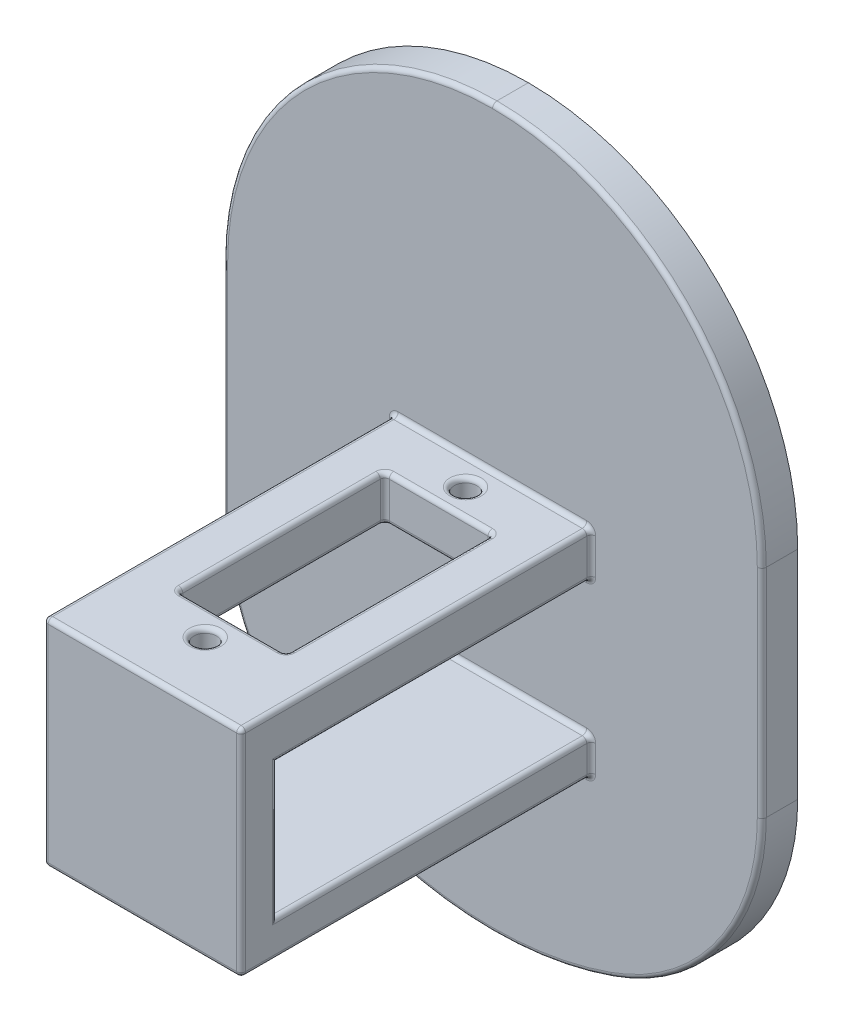
SolidWorks part; units mm, degrees
ref_plane "Front Plane" through (0, 0, 0) normal (0, 0, 1) x (1, 0, 0)
ref_plane "Top Plane" through (0, 0, 0) normal (0, 1, 0) x (1, 0, 0)
ref_plane "Right Plane" through (0, 0, 0) normal (1, 0, 0) x (0, 0, -1)
sketch "Sketch1" plane through (0, 0, 0) normal (0, 0, 1) x (1, 0, 0)
  circle A0 centre (0, 0) radius 40
  point P0 (0, 0)
  dimension "D1" = 80
extrude "Boss-Extrude1" add sketch "Sketch1" along normal blind 4
sketch "Sketch10" plane through (0, 0, 4) normal (0, 0, 1) x (1, 0, 0)
  line L0 (-30, 26.4575) -> (-30, -26.4575)
  line L1 (30, 26.4575) -> (30, -26.4575)
  arc A0 (30, -26.4575) -> (30, 26.4575) centre (0, 0) ccw
  circle A1 centre (0, 0) radius 40
  arc A2 (-30, 26.4575) -> (-30, -26.4575) centre (0, 0) ccw
  dimension "D2" = 30
  dimension "D3" = 60
  dimension "D1" = 0
extrude "Cut-Extrude3" cut sketch "Sketch10" against normal blind 10
fillet "Fillet1" radius 30 2 edges at (-30, 26.4575, 2) (30, 26.4575, 2)
fillet "Fillet2" radius 25 2 edges at (-30, -26.4575, 2) (30, -26.4575, 2)
sketch "Sketch4" plane through (0, 0, 4) normal (0, 0, 1) x (1, 0, 0)
  line L1 (-11, 4.5) -> (11, 4.5)
  line L2 (-11, 4.5) -> (-11, -0.5)
  line L3 (-11, -0.5) -> (11, -0.5)
  line L4 (11, 4.5) -> (11, -0.5)
  line L5 (-11, 4.5) -> (11, -0.5) construction
  line L6 (-11, -0.5) -> (11, 4.5) construction
  point P0 (0, 2)
  dimension "D1" = 22
  dimension "D2" = 5
  dimension "D3" = 2
extrude "Boss-Extrude2" add sketch "Sketch4" along normal blind 35
sketch "Sketch5" plane through (0, 4.5, 0) normal (0, 1, 0) x (1, 0, 0)
  line L1 (-6, -10) -> (6, -10)
  line L2 (-6, -10) -> (-6, -33)
  line L3 (-6, -33) -> (6, -33)
  line L4 (6, -10) -> (6, -33)
  line L5 (-6, -10) -> (6, -33) construction
  line L6 (-6, -33) -> (6, -10) construction
  line L7 (-11, -39) -> (-11, -4) construction
  line L8 (11, -39) -> (-11, -39) construction
  point P0 (0, -21.5)
  point P10 (-11, -21.5)
  point P12 (0, -39)
  dimension "D1" = 12
  dimension "D2" = 23
extrude "Cut-Extrude1" cut sketch "Sketch5" against normal blind 5
sketch "Sketch6" plane through (0, 4.5, 0) normal (0, 1, 0) x (1, 0, 0)
  line L0 (0, -7) -> (0, -36) construction
  line L1 (-6, -10) -> (-6, -33) construction
  line L2 (-6, -33) -> (6, -33) construction
  circle A0 centre (0, -7) radius 1.25
  circle A1 centre (0, -36) radius 1.25
  point P4 (0, -21.5)
  point P7 (-6, -21.5)
  point P10 (0, -33)
  dimension "D1" = 2.5
  dimension "D2" = 29
extrude "Cut-Extrude2" cut sketch "Sketch6" against normal blind 5
sketch "Sketch7" plane through (0, 0, 39) normal (0, 0, 1) x (1, 0, 0)
  line L0 (11, -0.5) -> (11, 4.5) construction
  line L1 (-11, 4.5) -> (11, 4.5)
  line L2 (-11, 4.5) -> (-11, -15.5)
  line L3 (-11, -15.5) -> (11, -15.5)
  line L4 (11, 4.5) -> (11, -15.5)
  line L5 (11, -0.5) -> (11, 4.5) construction
  dimension "D1" = 20
extrude "Boss-Extrude3" add sketch "Sketch7" along normal blind 4
sketch "Sketch8" plane through (0, -15.5, 0) normal (0, -1, 0) x (1, 0, 0)
  line L1 (-11, 43) -> (11, 43)
  line L2 (-11, 43) -> (-11, 4)
  line L3 (-11, 4) -> (11, 4)
  line L4 (11, 43) -> (11, 4)
extrude "Boss-Extrude4" add sketch "Sketch8" along normal blind 4
sketch "Sketch9" plane through (0, -19.5, 0) normal (0, -1, 0) x (1, 0, 0)
  line L0 (-11, 4) -> (11, 4) construction
  circle A0 centre (0, 26.5) radius 3.75
  dimension "D1" = 7.5
  dimension "D2" = 22.5
extrude "Boss-Extrude5" add sketch "Sketch9" along normal blind 7
fillet "Fillet3" radius 0.5 43 edges at (21.2132, 31.2132, 4) (-21.2132, 31.2132, 4) (-30, -2.0711, 4) (-25.4124, -28.5759, 4) (0, -40, 4) (25.4124, -28.5759, 4) (30, -2.0711, 4) (0, -19.5, 4) (-11, -17.5, 4) (11, -17.5, 4) (-11, -8, 39) (0, -15.5, 4) (11, -15.5, 21.5) (-11, -15.5, 21.5) (0, -26.5, 22.75) (-11, -0.5, 21.5) (-11, -19.5, 23.5) (0, -19.5, 43) (11, -19.5, 23.5) (11, -8, 39) (-11, -7.5, 43) (11, -7.5, 43) (11, -0.5, 21.5) (0, 4.5, 33) (6, 4.5, 21.5) (0, 4.5, 10) (-6, 4.5, 21.5) (-11, 4.5, 23.5) (0, 4.5, 43) (11, 4.5, 23.5) (0, -19.5, 22.75) (0, -0.5, 33) (-6, -0.5, 21.5) (-6, 2, 33) (0, -0.5, 10) (-6, 2, 10) (6, 2, 33) (6, -0.5, 21.5) (6, 2, 10) (0, 4.5, 4) (-11, 2, 4) (0, -0.5, 4) (11, 2, 4)
fillet "Fillet4" radius 0.5 2 edges at (0, 4.5, 37.25) (0, 4.5, 8.25)
